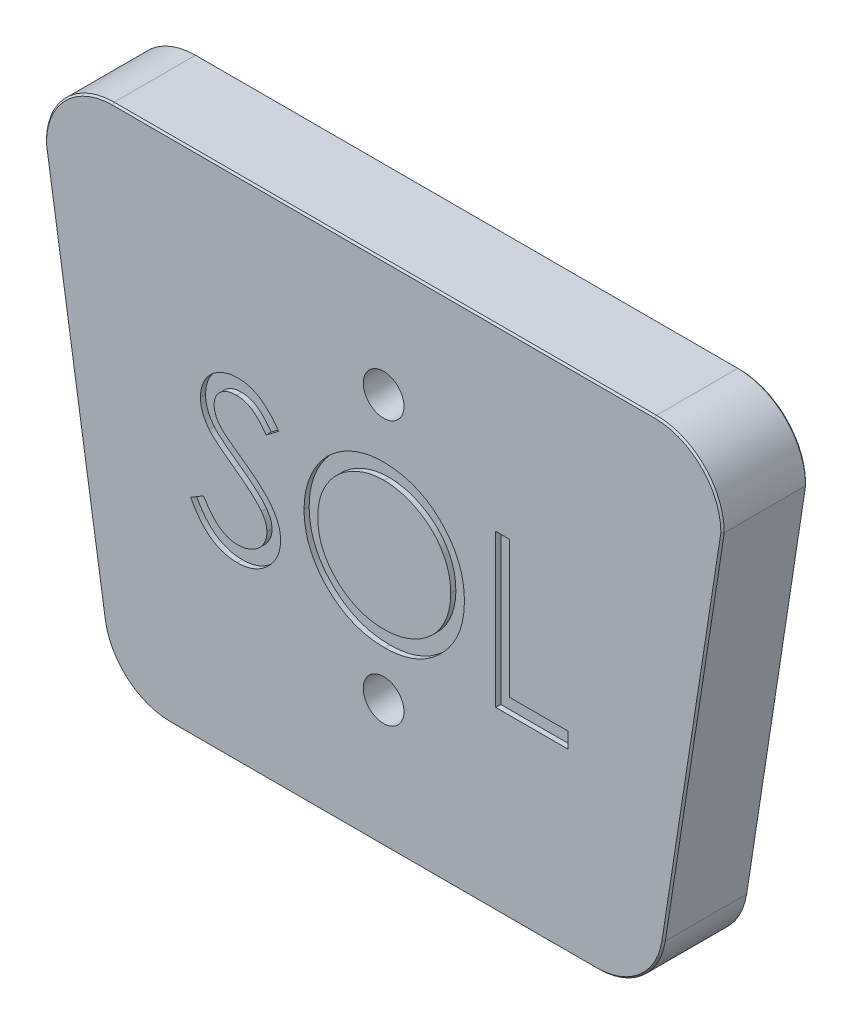
SolidWorks part; units mm, degrees
ref_plane "Front Plane" through (0, 0, 0) normal (0, 0, 1) x (1, 0, 0)
ref_plane "Top Plane" through (0, 0, 0) normal (0, 1, 0) x (1, 0, 0)
ref_plane "Right Plane" through (0, 0, 0) normal (1, 0, 0) x (0, 0, -1)
sketch "Sketch2" plane through (0, 0, 0) normal (0, 0, 1) x (1, 0, 0)
  line L0 (20, -150) -> (180, -150)
  line L1 (40, 0) -> (160, 0)
  line L3 (40, -150) -> (160, -150)
  line L6 (180, 0) -> (20, 0)
  line L8 (0, -20) -> (20, -150)
  line L9 (200, -20) -> (180, -150)
  arc A4 (200, -20) -> (180, 0) centre (180, -20) ccw
  arc A5 (0, -20) -> (20, 0) centre (20, -20) cw
  point P2 (200, 0)
  point P7 (0, -150)
  point P12 (200, 0)
  point P15 (0, 0)
  point P21 (0, 0)
  dimension "D3" = 20
  dimension "D1" = 200
  dimension "D2" = 150
extrude "Boss-Extrude1" add sketch "Sketch2" along normal blind 25 contours A5 L8 L0 L9 A4 L6 L1 region at (100, -72.4209, 0)
fillet "Fillet2" radius 20 2 edges at (180, -150, 12.5) (20, -150, 12.5)
sketch "Sketch10" plane through (0, 0, 25) normal (0, 0, 1) x (1, 0, 0)
  line L0 (100, 0) -> (100, -69) construction
  line L1 (180, 0) -> (20, 0) construction
  line L2 (37.1584, -150) -> (162.8416, -150) construction
  line L3 (100, 0) -> (100, -69) construction
  line L4 (100, -75) -> (100, -150) construction
  line L5 (100, 0) -> (100, -69) construction
  line L6 (100, -75) -> (100, -150) construction
  circle A1 centre (100, -112.5) radius 6
  circle A2 centre (100, -34.5) radius 6
  dimension "D1" = 12
extrude "Cut-Extrude6" cut sketch "Sketch10" against normal blind 12
sketch "Sketch11" plane through (0, 0, 13) normal (0, 0, 1) x (1, 0, 0)
  circle A0 centre (100, -34.5) radius 3.2
  circle A2 centre (100, -112.5) radius 3.2
  dimension "D1" = 6.4
extrude "Cut-Extrude7" cut sketch "Sketch11" against normal through all
sketch "Sketch13" plane through (0, 0, 25) normal (0, 0, 1) x (1, 0, 0)
  text T0 "SOL" font "Century Gothic" height 45
extrude "Cut-Extrude8" cut sketch "Sketch13" against normal blind 1.5
chamfer "Chamfer1" distance 0.5 angle 45 18 edges at (194.1421, -5.8579, 0) (100, 0, 0) (5.8579, -5.8579, 0) (8.6955, -76.5206, 0) (24.1358, -145.1793, 0) (100, -150, 0) (175.8642, -145.1793, 0) (191.3045, -76.5206, 0) (103.2, -112.5, 0) (103.2, -34.5, 0) (5.8579, -5.8579, 25) (100, 0, 25) (194.1421, -5.8579, 25) (191.3045, -76.5206, 25) (175.8642, -145.1793, 25) (100, -150, 25) (24.1358, -145.1793, 25) (8.6955, -76.5206, 25)
